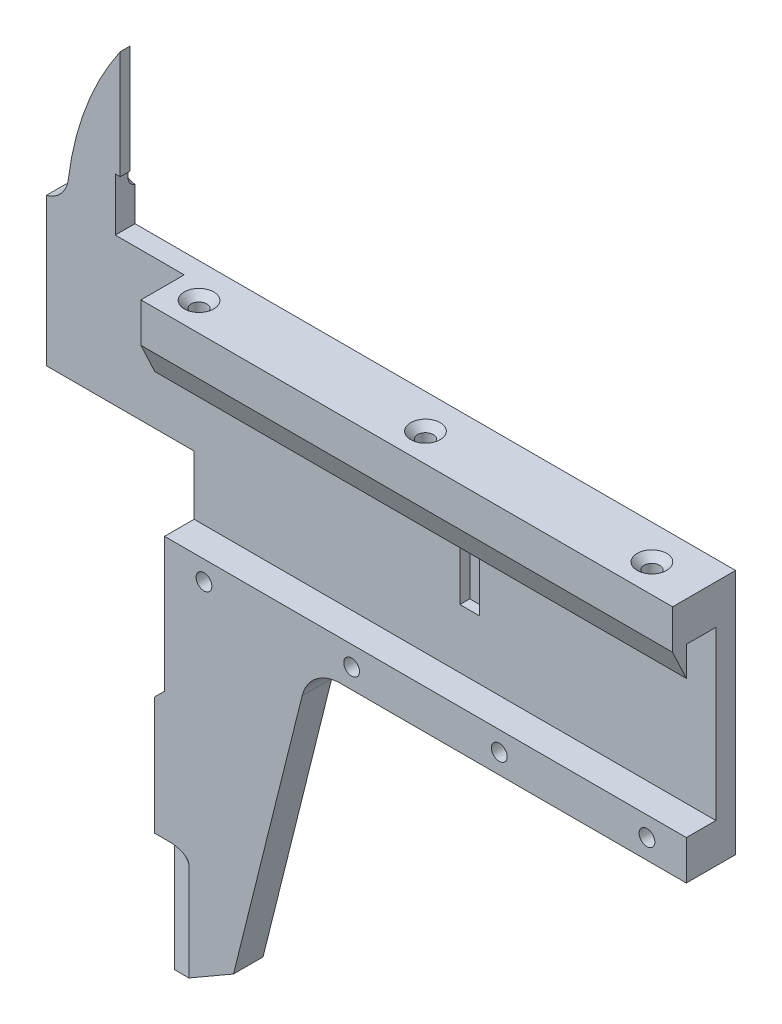
SolidWorks part; units mm, degrees
ref_plane "前视基准面" through (0, 0, 0) normal (0, 0, 1) x (1, 0, 0)
ref_plane "上视基准面" through (0, 0, 0) normal (0, 1, 0) x (1, 0, 0)
ref_plane "右视基准面" through (0, 0, 0) normal (1, 0, 0) x (0, 0, -1)
sketch "草图1" plane through (0, 0, 0) normal (0, 0, 1) x (1, 0, 0)
  line L0 (-53, -8) -> (-53, -14.62)
  line L1 (0, 0) -> (-53, 0)
  line L2 (0, 0) -> (0, -4)
  line L3 (0, -4) -> (-35.1436, -4)
  line L4 (-53, 0) -> (-53, -8)
  line L5 (-53, -14.62) -> (-54, -14.62)
  line L6 (-54, -14.62) -> (-54, -39.62)
  line L7 (-54, -39.62) -> (-45.9979, -35)
  line L8 (-45.9979, -35) -> (-39.0248, -7.0323)
  line L9 (3.6791, 0) -> (-3.6791, 0) construction
  arc A0 (-39.0248, -7.0323) -> (-35.1436, -4) centre (-35.1436, -8) cw
  point P12 (-53, -8)
  point P13 (0, 0)
  point P14 (0, 0)
  point P17 (-53, -23.3931)
  dimension "D7" = 4
  dimension "D1" = 4
  dimension "D2" = 53
  dimension "D3" = 1
  dimension "D4" = 120
  dimension "D5" = 31
  dimension "D6" = 104
  dimension "D8" = 39.62
  dimension "D9" = 14.62
extrude "凸台-拉伸1" add sketch "草图1" against normal blind 3
sketch "草图2" plane through (0, 0, -3) normal (0, 0, -1) x (-1, 0, 0)
  line L0 (53, 0) -> (53, -14.62) construction
  line L1 (0, -4) -> (53, -4)
  line L2 (0, -4) -> (0, 21)
  line L3 (0, 21) -> (53, 21)
  line L4 (53, -4) -> (53, 6)
  line L5 (53, 6) -> (68, 6)
  line L6 (68, 6) -> (68, 21)
  line L7 (68, 21) -> (65.9785, 21)
  line L8 (60.5033, 37.38) -> (60.5033, 26.38)
  line L9 (60.5033, 26.38) -> (61.0033, 26.38)
  line L10 (61.0033, 26.38) -> (61.0033, 21)
  line L11 (61.0033, 21) -> (53, 21)
  line L12 (53, 6) -> (53, 21) construction
  arc A0 (65.9785, 21) -> (60.5033, 37.38) centre (35.0036, 19.7514) ccw
  point P10 (66.1685, 21)
  point P28 (119.24, 19.7514)
  dimension "D4" = 31
  dimension "D5" = 2.0215
  dimension "D1" = 25
  dimension "D2" = 15
  dimension "D3" = 15
  dimension "D6" = 0.5
  dimension "D7" = 11
  dimension "D8" = 16.38
extrude "凸台-拉伸2" add sketch "草图2" along normal blind 2
fillet "圆角1" radius 2 1 edges at (-44.0718, -4, -3)
fillet "圆角2" radius 3 1 edges at (-65.9785, 21, -4)
chamfer "倒角1" distance 1 angle 45 1 edges at (-53, -14.62, -1.5)
sketch "草图3" plane through (0, 0, 0) normal (1, 0, 0) x (0, 0, -1)
  line L0 (0, 17) -> (0, 14)
  line L1 (3, 21) -> (-1.3989, 21)
  line L2 (3, 21) -> (3, 17)
  line L3 (3, 17) -> (0, 17)
  line L4 (-1.3989, 21) -> (-1.3989, 17)
  line L5 (3, 26.38) -> (3, 21) construction
  line L6 (0, 14) -> (-1.3989, 17)
  line L7 (0, 17) -> (-1.3989, 17) construction
  dimension "D1" = 4
  dimension "D2" = 3
  dimension "D3" = 155
  dimension "D4" = 7
extrude "凸台-拉伸3" add sketch "草图3" against normal blind 54
sketch "草图5" plane through (0, 0, 0) normal (0, 0, 1) x (1, 0, 0)
  line L0 (-35.1436, -4) -> (0, -4) construction
  line L1 (0, -3.6791) -> (0, 3.6791) construction
  point P0 (-4, -2)
  dimension "D1" = 2
  dimension "D2" = 4
hole_wizard "M2 螺纹孔1" positions "草图5" profile "草图6" tap size "M2" standard "GB"
sketch "草图6" plane through (-4, -2, 0) normal (1, 0, 0) x (0, -1, 0)
  line L0 (0, 0) -> (0, 4.4807)
  line L1 (0, 4.4807) -> (0.8, 4)
  line L2 (0.8, 4) -> (0.8, 0)
  line L5 (0.8, 0) -> (0, 0)
  line L10 (0, 4.4807) -> (-0.8, 4) construction
  line L11 (0, -6.35) -> (0, 107.95) construction
  dimension "螺纹孔钻头直径" = 1.6
  dimension "螺纹孔钻头深度" = 4
  dimension "导头角度" = 118
cosmetic thread "孔螺纹线1" parameters "D1"=4, "D2"=2
pattern_linear "阵列(线性)1" count 4 spacing 15 along (-1, 0, 0) of "M2 螺纹孔1"
cosmetic thread "孔螺纹线2" parameters "D1"=4, "D2"=2
cosmetic thread "孔螺纹线3" parameters "D1"=4, "D2"=2
cosmetic thread "孔螺纹线4" parameters "D1"=4, "D2"=2
sketch "草图7" plane through (0, 21, 0) normal (0, 1, 0) x (1, 0, 0)
  line L0 (0, -3.6791) -> (0, 3.6791) construction
  line L1 (-61.0033, 5) -> (0, 5) construction
  point P0 (-5, 1.5)
  point P5 (0, 3)
  dimension "D1" = 5
  dimension "D2" = 3.5
hole_wizard "M2 螺纹孔2" positions "草图7" profile "草图8" tap size "M2" standard "GB" end condition up to next
sketch "草图8" plane through (-5, 21, -1.5) normal (1, 0, 0) x (0, 0, 1)
  line L0 (0, 0) -> (0, 4)
  line L1 (0, 4) -> (0.8, 4)
  line L2 (0.8, 4) -> (0.8, 0.7)
  line L3 (0.8, 0.7) -> (1.5, 0)
  line L5 (1.5, 0) -> (0, 0)
  line L6 (-0.8, 0.7) -> (-1.5, 0) construction
  line L11 (0, -6.35) -> (0, 107.95) construction
  dimension "通孔螺纹孔钻头直径" = 1.6
  dimension "通孔螺纹孔钻头深度" = 4
  dimension "近端锥形沉头孔直径" = 3
  dimension "近端锥形沉头孔角度" = 90
cosmetic thread "孔螺纹线5" parameters "D2"=2
pattern_linear "阵列(线性)2" count 3 spacing 23 along (-1, 0, 0) of "M2 螺纹孔2"
cosmetic thread "孔螺纹线6" parameters "D2"=2
cosmetic thread "孔螺纹线7" parameters "D2"=2
ref_plane "基准面1" through (0, 37.38, 0) normal (0, 1, 0) x (1, 0, 0)
sketch "草图9" plane through (0, 37.38, 0) normal (0, 1, 0) x (1, 0, 0)
  line L0 (-60.5033, 4) -> (-62.2354, 5)
  line L1 (-60.5033, 5) -> (-60.5033, 3) construction
  line L2 (-60.5033, 5) -> (-65.7714, 5) construction
  line L3 (-65.7714, 3) -> (-60.5033, 3) construction
  line L6 (-62.2354, 5) -> (-60.5033, 5)
  line L7 (-60.5033, 5) -> (-60.5033, 4)
  dimension "D1" = 30
  dimension "D2" = 1
extrude "切除-拉伸1" cut sketch "草图9" against normal blind 13
fillet "圆角3" radius 1 1 edges at (-61.6193, 24.38, -4.6443)
ref_plane "基准面2" through (0, -39.62, 0) normal (0, 1, 0) x (1, 0, 0)
sketch "草图10" plane through (0, -39.62, 0) normal (0, 1, 0) x (1, 0, 0)
  line L0 (-54, 2) -> (-50.5359, 0)
  line L1 (-54, 3) -> (-54, 0) construction
  line L2 (-54, 0) -> (-45.9979, 0) construction
  line L4 (-54, 3) -> (-45.9979, 3) construction
  line L5 (-50.5359, 0) -> (-54, 0)
  line L6 (-54, 0) -> (-54, 2)
  dimension "D1" = 1
  dimension "D2" = 30
extrude "切除-拉伸2" cut sketch "草图10" along normal blind 13
fillet "圆角4" radius 1 1 edges at (-52.2679, -26.62, -1)
sketch "草图11" plane through (0, 0, -3) normal (0, 0, 1) x (1, 0, 0)
  line L0 (0, 0) -> (-53, 0) construction
  line L1 (-26, 6) -> (-24, 6)
  line L2 (-26, 6) -> (-26, 11)
  line L3 (-26, 11) -> (-24, 11)
  line L4 (-24, 6) -> (-24, 11)
  line L5 (0, 17) -> (0, 0) construction
  dimension "D1" = 5
  dimension "D2" = 2
  dimension "D3" = 6
  dimension "D4" = 26
extrude "切除-拉伸3" cut sketch "草图11" against normal blind 1
